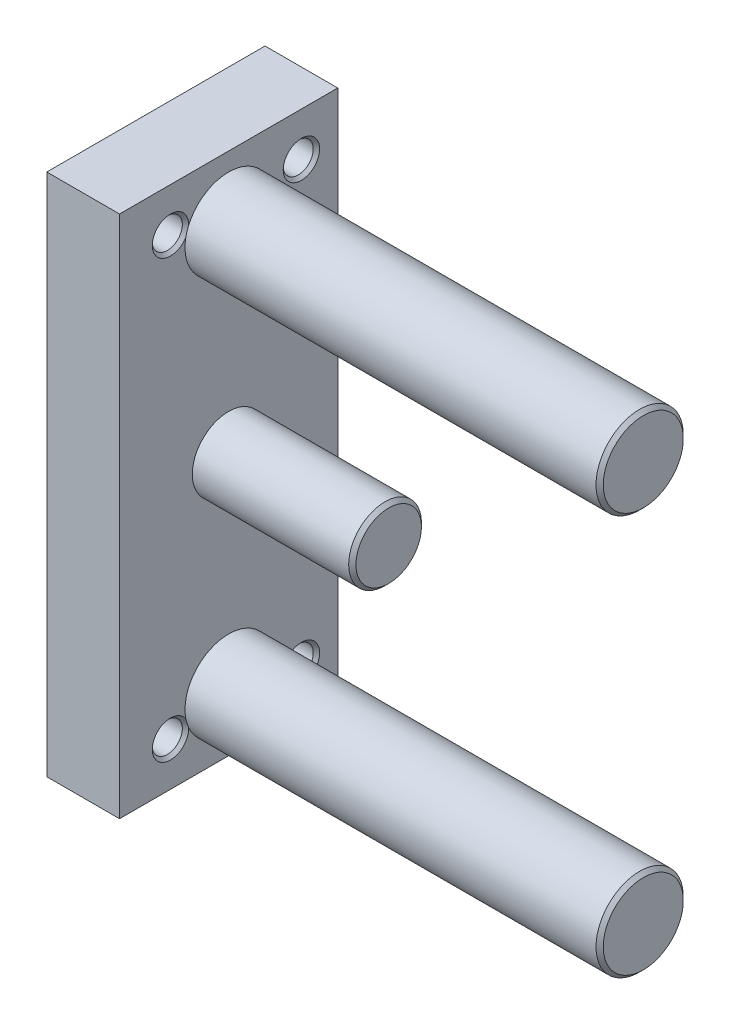
SolidWorks part; units mm, degrees
ref_plane "前视基准面" through (0, 0, 0) normal (0, 0, 1) x (1, 0, 0)
ref_plane "上视基准面" through (0, 0, 0) normal (0, 1, 0) x (1, 0, 0)
ref_plane "右视基准面" through (0, 0, 0) normal (1, 0, 0) x (0, 0, -1)
sketch "草图1" plane through (0, 0, 0) normal (1, 0, 0) x (0, 0, -1)
  line L0 (-15, -36) -> (15, -36)
  line L1 (15, -36) -> (15, 36)
  line L2 (15, 36) -> (-15, 36)
  line L3 (-15, 36) -> (-15, -36)
extrude "凸台-拉伸1" add sketch "草图1" along normal blind 10
ref_plane "基准面4" through (0, 30, 0) normal (0, 1, 0) x (1, 0, 0)
sketch "草图2" plane through (0, 30, 0) normal (0, 1, 0) x (1, 0, 0)
  line L0 (0, 10) -> (0, 12.5)
  line L1 (0, 12.5) -> (0.433, 12.067)
  line L2 (0.433, 12.067) -> (9.567, 12.067)
  line L3 (9.567, 12.067) -> (10, 12.5)
  line L4 (10, 12.5) -> (10, 10)
  line L5 (10, 10) -> (0, 10)
  line L6 (10, 10) -> (0, 10) construction
revolve "切除-旋转1" cut sketch "草图2" angle 360 about L6 reverse direction yes
cosmetic thread "装饰螺纹线1" parameters "D1"=10, "D2"=5
sketch "草图3" plane through (0, 0, 0) normal (1, 0, 0) x (0, 0, -1)
  line L0 (10, 30) -> (-990, 30)
  line L1 (10, 30) -> (10, -970)
pattern_linear "阵列(线性)1" count 2 spacing 18 along (0, 0, 1) count 2 spacing 60 along (0, -1, 0) of "切除-旋转1"
ref_plane "基准面5" through (0, 27.5, 0) normal (0, 1, 0) x (1, 0, 0)
sketch "草图4" plane through (0, 27.5, 0) normal (0, 1, 0) x (1, 0, 0)
  line L0 (0, 0) -> (0, 3.8)
  line L1 (0, 3.8) -> (5.5556, 3.8)
  line L2 (5.5556, 3.8) -> (5.5556, 3.5)
  line L3 (5.5556, 3.5) -> (2.0556, 3.5)
  line L4 (2.0556, 3.5) -> (1.5556, 3)
  line L5 (1.5556, 3) -> (1.5556, 1.5)
  line L6 (1.5556, 1.5) -> (4.1556, 1.5)
  line L7 (4.1556, 1.5) -> (5.0216, 0)
  line L8 (5.0216, 0) -> (0, 0)
  line L9 (5.0216, 0) -> (0, 0) construction
revolve "切除-旋转2" cut sketch "草图4" angle 360 about L9 reverse direction yes
sketch "草图5" plane through (0, 0, 0) normal (0, 1, 0) x (1, 0, 0)
  line L0 (0, 0) -> (0, 3.8)
  line L1 (0, 3.8) -> (5.5556, 3.8)
  line L2 (5.5556, 3.8) -> (5.5556, 3.5)
  line L3 (5.5556, 3.5) -> (2.0556, 3.5)
  line L4 (2.0556, 3.5) -> (1.5556, 3)
  line L5 (1.5556, 3) -> (1.5556, 1.5)
  line L6 (1.5556, 1.5) -> (4.1556, 1.5)
  line L7 (4.1556, 1.5) -> (5.0216, 0)
  line L8 (5.0216, 0) -> (0, 0)
  line L9 (5.0216, 0) -> (0, 0) construction
revolve "切除-旋转3" cut sketch "草图5" angle 360 about L9 reverse direction yes
ref_plane "基准面6" through (0, -27.5, 0) normal (0, 1, 0) x (1, 0, 0)
sketch "草图6" plane through (0, -27.5, 0) normal (0, 1, 0) x (1, 0, 0)
  line L0 (0, 0) -> (0, 3.8)
  line L1 (0, 3.8) -> (5.5556, 3.8)
  line L2 (5.5556, 3.8) -> (5.5556, 3.5)
  line L3 (5.5556, 3.5) -> (2.0556, 3.5)
  line L4 (2.0556, 3.5) -> (1.5556, 3)
  line L5 (1.5556, 3) -> (1.5556, 1.5)
  line L6 (1.5556, 1.5) -> (4.1556, 1.5)
  line L7 (4.1556, 1.5) -> (5.0216, 0)
  line L8 (5.0216, 0) -> (0, 0)
  line L9 (5.0216, 0) -> (0, 0) construction
revolve "切除-旋转4" cut sketch "草图6" angle 360 about L9 reverse direction yes
sketch "草图7" plane through (0, 0, 0) normal (0, 1, 0) x (1, 0, 0)
  line L0 (10, 0) -> (10, 5)
  line L1 (10, 5) -> (31.5, 5)
  line L2 (31.5, 5) -> (32, 4.5)
  line L3 (32, 4.5) -> (32, 0)
  line L4 (32, 0) -> (10, 0)
  line L5 (32, 0) -> (10, 0) construction
revolve "旋转1" add sketch "草图7" angle 360 about L5 reverse direction yes
ref_plane "基准面7" through (0, -27.5, 0) normal (0, 1, 0) x (1, 0, 0)
sketch "草图8" plane through (0, -27.5, 0) normal (0, 1, 0) x (1, 0, 0)
  line L0 (10, 0) -> (10, 6)
  line L1 (10, 6) -> (66.5, 6)
  line L2 (66.5, 6) -> (67, 5.5)
  line L3 (67, 5.5) -> (67, 0)
  line L4 (67, 0) -> (10, 0)
  line L5 (67, 0) -> (10, 0) construction
revolve "旋转2" add sketch "草图8" angle 360 about L5 reverse direction yes
ref_plane "基准面8" through (0, 27.5, 0) normal (0, 1, 0) x (1, 0, 0)
sketch "草图9" plane through (0, 27.5, 0) normal (0, 1, 0) x (1, 0, 0)
  line L0 (10, 0) -> (10, 6)
  line L1 (10, 6) -> (66.5, 6)
  line L2 (66.5, 6) -> (67, 5.5)
  line L3 (67, 5.5) -> (67, 0)
  line L4 (67, 0) -> (10, 0)
  line L5 (67, 0) -> (10, 0) construction
revolve "旋转3" add sketch "草图9" angle 360 about L5 reverse direction yes
ref_plane "基准面9" through (12, 0, 0) normal (1, 0, 0) x (0, 0, -1)
ref_plane "s XY" through (12, 0, 0) normal (1, 0, 0) x (0, 0, -1)
ref_plane "s XZ" through (0, 0, 0) normal (0, -1, 0) x (-1, 0, 0)
ref_plane "s YZ" through (0, 0, 0) normal (0, 0, -1) x (-1, 0, 0)
ref_axis "s X" through (12, 0, 80.9) along (0, 0, -1)
ref_axis "s Y" through (12, -50, 0) along (0, 1, 0)
ref_axis "s Z" through (80.9, 0, 0) along (-1, 0, 0)
sketch3d "s"
  point P0 (12, 0, 0)
